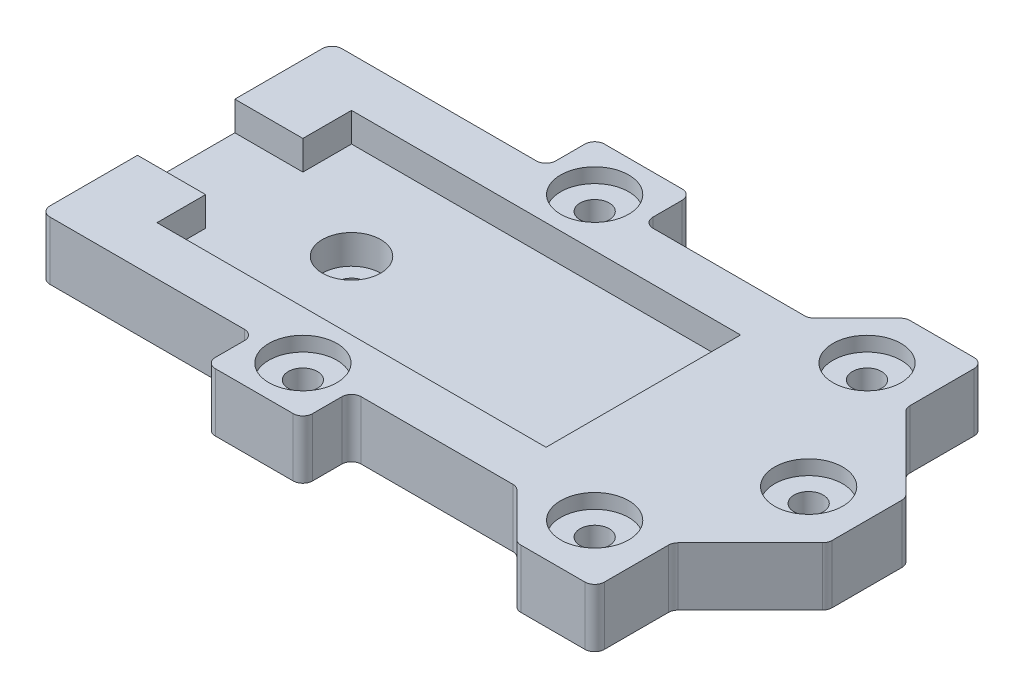
SolidWorks part; units mm, degrees
material "ABS"
ref_plane "前视基准面" through (0, 0, 0) normal (0, 0, 1) x (1, 0, 0)
ref_plane "上视基准面" through (0, 0, 0) normal (0, 1, 0) x (1, 0, 0)
ref_plane "右视基准面" through (0, 0, 0) normal (1, 0, 0) x (0, 0, -1)
sketch "草图1" plane through (0, 0, 0) normal (0, 1, 0) x (1, 0, 0)
  line L0 (0, 26.7143) -> (0, -26.4286) construction
  line L1 (-27, -15) -> (27, -15)
  line L2 (-27, -15) -> (-27, 15)
  line L3 (-27, 15) -> (27, 15)
  line L4 (27, -15) -> (27, 15)
  line L5 (-27, -15) -> (27, 15) construction
  line L6 (-27, 15) -> (27, -15) construction
  line L7 (-43.6667, 0) -> (48.8095, 0) construction
  line L8 (-5, 15) -> (-5, 20)
  line L9 (-5, 20) -> (5, 20)
  line L10 (5, 20) -> (5, 15)
  line L11 (5, -20) -> (5, -15)
  line L12 (-5, -20) -> (5, -20)
  line L13 (-5, -15) -> (-5, -20)
  line L14 (22, 15) -> (27, 20)
  line L15 (27, 20) -> (35, 20)
  line L16 (35, 20) -> (35, 12)
  line L17 (35, 12) -> (43, 4)
  line L18 (43, 4) -> (43, -4)
  line L19 (35, -12) -> (43, -4)
  line L20 (35, -20) -> (35, -12)
  line L21 (27, -20) -> (35, -20)
  line L22 (22, -15) -> (27, -20)
  circle A0 centre (0, 15) radius 1.5
  circle A1 centre (0, -15) radius 1.5
  circle A2 centre (29, 14) radius 1.5
  circle A3 centre (37, 0) radius 1.5
  circle A4 centre (29, -14) radius 1.5
  point P0 (0, 0)
  point P25 (43, 0)
  dimension "D10" = 3
  dimension "D11" = 3
  dimension "D13" = 3
  dimension "D1" = 30
  dimension "D2" = 54
  dimension "D3" = 5
  dimension "D4" = 10
  dimension "D5" = 5
  dimension "D6" = 8
  dimension "D7" = 5
  dimension "D8" = 8
  dimension "D9" = 4
  dimension "D12" = 6
  dimension "D14" = 6
  dimension "D15" = 6
extrude "凸台-拉伸1" add sketch "草图1" along normal blind 6 contours L1 A1 L4 L3 A0 L2 | A0 L3 L10 L9 L8 | L1 A1 L13 L12 L11 | L1 L22 L21 L20 L19 L18 L17 L16 L15 L14 L3 L4 A2 A3 A4 region at (0, 0, 0) region at (0, 0, 17.6417) region at (0, 0, -17.6417) region at (32.7328, 0, 0)
sketch "草图2" plane through (0, 6, 0) normal (0, 1, 0) x (1, 0, 0)
  line L0 (-20, 10) -> (-20, -10)
  line L1 (-20, -10) -> (20, -10)
  line L2 (20, -10) -> (20, 10)
  line L3 (20, 10) -> (-20, 10)
  line L4 (-27, -15) -> (-27, 15) construction
  line L5 (-27, 15) -> (-5, 15) construction
  line L6 (-32.9754, 0) -> (48.8868, 0) construction
  line L7 (-20, 5) -> (-27, 5)
  line L8 (-27, 5) -> (-27, -5)
  line L9 (-27, -5) -> (-20, -5)
  line M14 (-27, 15) -> (-27, -15)
  dimension "D1" = 7
  dimension "D2" = 5
  dimension "D3" = 20
  dimension "D4" = 40
  dimension "D5" = 10
extrude "切除-拉伸1" cut sketch "草图2" against normal blind 3 contours L6 L0 L7 M14 | L6 L8 L9 L0 | L0 L6 L2 L3 | L6 L0 L1 L2 region at (0, 6, -5) region at (-23.5, 6, -2.5) region at (0, 6, 5) region at (-23.5, 6, 2.5)
sketch "草图3" plane through (0, 6, 0) normal (0, 1, 0) x (1, 0, 0)
  circle A0 centre (0, 15) radius 3.5
  circle A1 centre (0, -15) radius 3.5
  circle A2 centre (29, -14) radius 3.5
  circle A3 centre (37, 0) radius 3.5
  circle A4 centre (29, 14) radius 3.5
  dimension "D1" = 7
  dimension "D2" = 7
  dimension "D3" = 7
  dimension "D4" = 7
  dimension "D5" = 7
extrude "切除-拉伸2" cut sketch "草图3" against normal blind 1.5
sketch "草图5" plane through (0, 3, 0) normal (0, 1, 0) x (1, 0, 0)
  line L0 (-31.0228, 0) -> (46.5369, 0) construction
  line L1 (-20, 10) -> (-20, 5) construction
  circle A0 centre (-10, 0) radius 3
  dimension "D1" = 10
  dimension "D2" = 6
extrude "切除-拉伸3" cut sketch "草图5" against normal blind 3
sketch "草图6" plane through (0, 0, 0) normal (0, -1, 0) x (1, 0, 0)
  circle A0 centre (-10, 0) radius 6
  dimension "D1" = 12
extrude "凸台-拉伸2" add sketch "草图6" along normal blind 3.5
sketch "草图7" plane through (0, -3.5, 0) normal (0, -1, 0) x (1, 0, 0)
  circle A0 centre (-10, 0) radius 3
  dimension "D1" = 6
extrude "切除-拉伸4" cut sketch "草图7" against normal blind 1
sketch "草图8" plane through (0, -2.5, 0) normal (0, -1, 0) x (1, 0, 0)
  circle A0 centre (-10, 0) radius 1.5
  dimension "D1" = 3
extrude "切除-拉伸5" cut sketch "草图8" against normal through all
fillet "圆角1" radius 1 20 edges at (27, 3, 20) (22, 3, 15) (5, 3, 15) (5, 3, 20) (-5, 3, 20) (-5, 3, 15) (-27, 3, 15) (-27, 3, -15) (-5, 3, -15) (27, 3, -20) (-5, 3, -20) (5, 3, -20) (5, 3, -15) (22, 3, -15) (35, 3, -20) (35, 3, -12) (43, 3, -4) (43, 3, 4) (35, 3, 12) (35, 3, 20)
